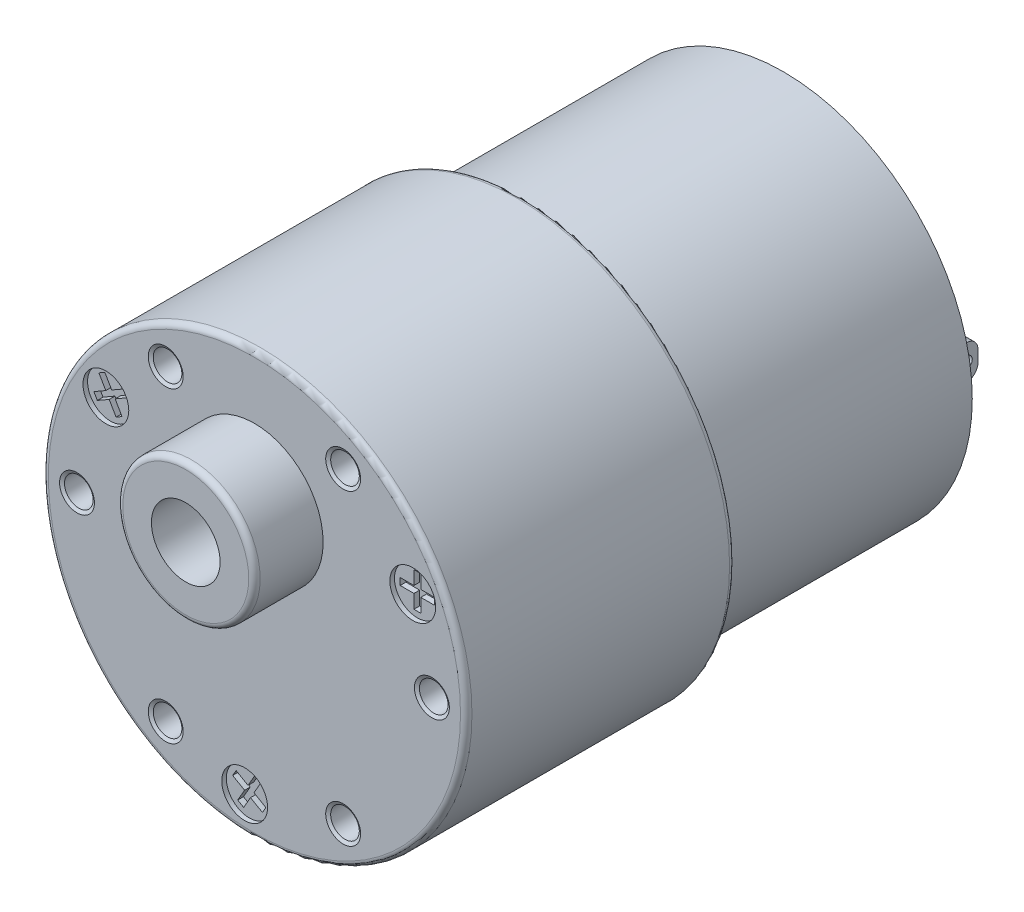
SolidWorks part; units mm, degrees
material "氧化铝"
ref_plane "前视基准面" through (0, 0, 0) normal (0, 0, 1) x (1, 0, 0)
ref_plane "上视基准面" through (0, 0, 0) normal (0, 1, 0) x (1, 0, 0)
ref_plane "右视基准面" through (0, 0, 0) normal (1, 0, 0) x (0, 0, -1)
sketch "草图1" plane through (0, 0, 0) normal (0, 0, 1) x (1, 0, 0)
  circle A0 centre (0, 0) radius 16.5
extrude "凸台-拉伸1" add sketch "草图1" along normal blind 22.7
sketch "草图2" plane through (0, 0, 22.7) normal (0, 0, 1) x (1, 0, 0)
  circle A0 centre (0, 0) radius 18.5
  dimension "D1" = 37
extrude "凸台-拉伸2" add sketch "草图2" along normal blind 23.5
sketch "草图3" plane through (0, 0, 46.2) normal (0, 0, 1) x (1, 0, 0)
  line L0 (0, 18.2228) -> (0, -18.5) construction
  circle A0 centre (0, 0) radius 18.5 construction
  circle A1 centre (0, 7) radius 6
  dimension "D1" = 7
extrude "凸台-拉伸3" add sketch "草图3" along normal blind 6
sketch "草图4" plane through (0, 0, 52.2) normal (0, 0, 1) x (1, 0, 0)
  circle A0 centre (0, 7) radius 3
extrude "凸台-拉伸4" add sketch "草图4" along normal blind 15.5
sketch "草图5" plane through (0, 0, 67.7) normal (0, 0, 1) x (1, 0, 0)
  line L0 (-1.6583, 9.5) -> (1.6583, 9.5)
  circle A0 centre (0, 7) radius 3 construction
  arc A1 (1.6583, 9.5) -> (-1.6583, 9.5) centre (0, 7) ccw
  dimension "D1" = 2.5
extrude "切除-拉伸1" cut sketch "草图5" against normal blind 12
sketch "草图6" plane through (0, 0, 0) normal (0, 0, -1) x (-1, 0, 0)
  line L0 (0, 18.5) -> (0, -18.5) construction
  line L1 (-18.5, 0) -> (18.5, 0) construction
  line L2 (-13.5, -1.5) -> (-12.5, -1.5)
  line L3 (-13.5, 1.5) -> (-12.5, 1.5)
  line L4 (-13.5, 1.5) -> (-13.5, -1.5)
  line L5 (12.5, 1.5) -> (12.5, -1.5)
  line L6 (-12.5, 1.5) -> (-12.5, -1.5)
  line L7 (13.5, 1.5) -> (13.5, -1.5)
  line L8 (13.5, 1.5) -> (12.5, 1.5)
  line L9 (13.5, -1.5) -> (12.5, -1.5)
  circle A1 centre (0, 0) radius 18.5 construction
  point P12 (-12.5, 0)
  point P16 (-13.5, 0)
  point P20 (13.5, 0)
  point P21 (12.5, 0)
  dimension "D1" = 1
  dimension "D2" = 1.5
  dimension "D3" = 5
extrude "凸台-拉伸5" add sketch "草图6" along normal blind 3.5
sketch "草图7" plane through (0, 0, 0) normal (0, 0, -1) x (-1, 0, 0)
  circle A0 centre (0, 0) radius 1.5
extrude "凸台-拉伸6" add sketch "草图7" along normal blind 1.5
sketch "草图8" plane through (13.5, 0, 0) normal (1, 0, 0) x (0, 0, -1)
  line L0 (3.5, 1.5) -> (3.5, -1.5) construction
  circle A0 centre (2.5, 0) radius 0.5
  point P2 (3.5, 0)
  dimension "D1" = 1
extrude "切除-拉伸2" cut sketch "草图8" against normal through all
fillet "圆角5" radius 1 4 edges at (-13, 1.5, -3.5) (-13, -1.5, -3.5) (13, 1.5, -3.5) (13, -1.5, -3.5)
hole_wizard "M3 螺纹孔3" positions "草图14" profile "草图13" tap size "M3" standard "Gb"
sketch "草图14" plane through (0, 0, 46.2) normal (0, 0, 1) x (1, 0, 0)
  line L0 (0, 0) -> (0, 18.5) construction
  line L3 (0, 0) -> (7.75, 13.4234) construction
  circle A0 centre (0, 0) radius 18.5 construction
  circle A1 centre (0, 0) radius 15.5 construction
  point P12 (7.75, 13.4234)
  dimension "D1" = 30
  dimension "D2" = 31
sketch "草图13" plane through (7.75, 13.4234, 46.2) normal (1, 0, 0) x (0, -1, 0)
  line L0 (0, 0) -> (0, 7.2511)
  line L1 (0, 7.2511) -> (1.25, 6.5)
  line L2 (1.25, 6.5) -> (1.25, 0.1588)
  line L3 (1.25, 0.1588) -> (1.525, 0)
  line L5 (1.525, 0) -> (0, 0)
  line L6 (-1.25, 0.1588) -> (-1.525, 0) construction
  line L10 (0, 7.2511) -> (-1.25, 6.5) construction
  line L11 (0, -6.35) -> (0, 107.95) construction
  dimension "螺纹孔钻头直径" = 2.5
  dimension "螺纹孔钻头深度" = 6.5
  dimension "近端锥形沉头孔直径" = 3.05
  dimension "近端锥形沉头孔角度" = 120
  dimension "导头角度" = 118
cosmetic thread "孔螺蚊线3" parameters "D1"=4, "D2"=3
ref_axis "基准轴1" through (0, 0, -7.35) along (0, 0, 1)
pattern_circular "阵列(圆周)1" count 6 over 360 about axis through (0, 0, -7.35) along (0, 0, 1) of "M3 螺纹孔3"
sketch "草图15" plane through (0, 0, 46.2) normal (0, 0, 1) x (1, 0, 0)
  circle A0 centre (13.8293, 7) radius 2
  circle A1 centre (0, 0) radius 15.5 construction
  dimension "D1" = 7
extrude "切除-拉伸3" cut sketch "草图15" against normal blind 0.4
sketch "草图17" plane through (0, 0, 45.8) normal (0, 0, 1) x (1, 0, 0)
  line L0 (13.8293, 9) -> (13.8293, 5) construction
  line L1 (11.8293, 7) -> (15.8293, 7) construction
  line L2 (13.5293, 5.5) -> (13.5293, 6.7)
  line L3 (13.5293, 8.5) -> (14.1293, 8.5)
  line L4 (14.1293, 5.5) -> (14.1293, 6.7)
  line L5 (13.8293, 7) -> (15.1633, 5.666) construction
  line L6 (12.3293, 7.3) -> (12.3293, 6.7)
  line L7 (15.3293, 6.7) -> (14.1293, 6.7)
  line L8 (15.3293, 7.3) -> (14.1293, 7.3)
  line L9 (13.5293, 6.7) -> (12.3293, 6.7)
  line L10 (13.5293, 7.3) -> (12.3293, 7.3)
  line L11 (13.5293, 5.5) -> (14.1293, 5.5)
  line L12 (15.3293, 7.3) -> (15.3293, 6.7)
  line L13 (13.5293, 7.3) -> (13.5293, 8.5)
  line L15 (14.1293, 7.3) -> (14.1293, 8.5)
  circle A0 centre (13.8293, 7) radius 2 construction
  circle A1 centre (13.8293, 7) radius 2 construction
  point P9 (13.8293, 5.5)
  point P13 (13.8293, 8.5)
  point P21 (14.1293, 7)
  point P22 (13.5293, 7)
  dimension "D1" = 0.3
  dimension "D2" = 1.5
extrude "切除-拉伸4" cut sketch "草图17" against normal blind 0.5
pattern_circular "阵列(圆周)2" count 3 over 360 about axis through (0, 0, -7.35) along (0, 0, 1) of "切除-拉伸3", "切除-拉伸4"
fillet "圆角6" radius 0.5 3 edges at (6, 7, 52.2) (18.5, 0, 46.2) (18.5, 0, 22.7)
sketch "草图18" plane through (0, 0, 0) normal (0, 0, -1) x (-1, 0, 0)
  circle A0 centre (0, 0) radius 16
extrude "切除-拉伸5" cut sketch "草图18" against normal blind 0.6
fillet "圆角7" radius 0.2 1 edges at (-1.5, 0, -1.5)
chamfer "倒角1" distance 0.3 angle 45 2 edges at (0, 9.5, 67.7) (0, 4, 67.7)
sketch "草图19" plane through (0, 0, 0) normal (1, 0, 0) x (0, 0, -1)
  line L0 (22.4957, 7) -> (-142.0758, 7)
sketch "草图20" plane through (0, 0, 46.2) normal (0, 0, 1) x (1, 0, 0)
  line L0 (0, 18.5) -> (0, -18.5)
  circle A0 centre (0, 0) radius 18.5 construction
sketch "Croquis1" plane through (0, 0, 67.7) normal (0, 0, 1) x (1, 0, 0)
  circle A0 centre (0, 7) radius 3
  dimension "D1" = 6
extrude "Cortar-Extruir1" cut sketch "Croquis1" against normal blind 22
